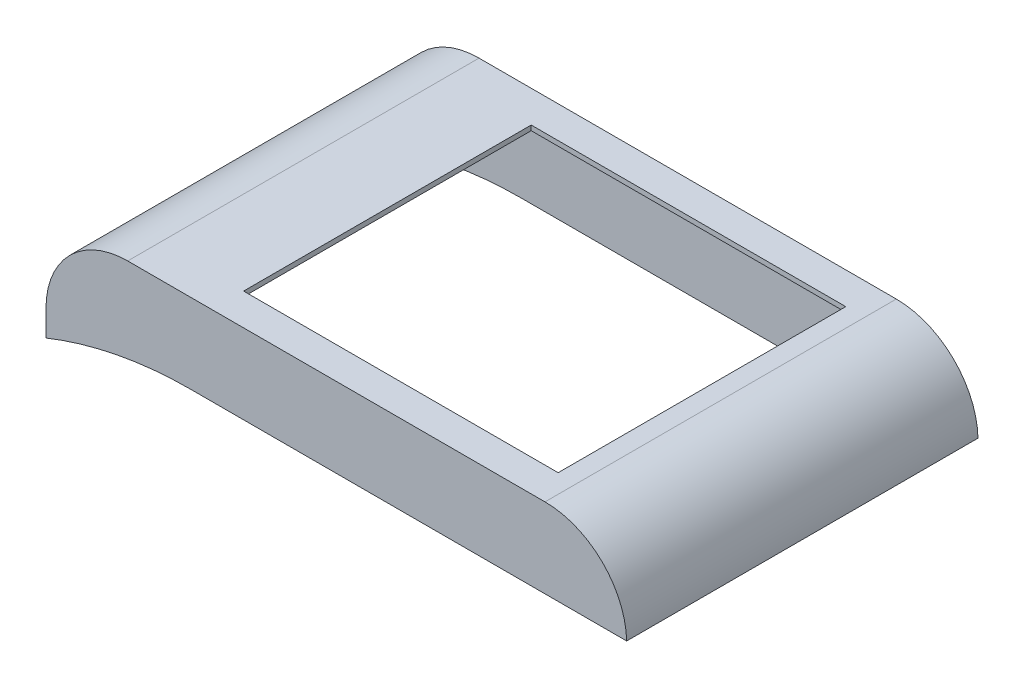
SolidWorks part; units mm, degrees
ref_plane "Front Plane" through (0, 0, 0) normal (0, 0, 1) x (1, 0, 0)
ref_plane "Top Plane" through (0, 0, 0) normal (0, 1, 0) x (1, 0, 0)
ref_plane "Right Plane" through (0, 0, 0) normal (1, 0, 0) x (0, 0, -1)
ref_plane "Plane1" through (0, 0, 21.5) normal (0, 0, 1) x (1, 0, 0)
sketch "Sketch1" plane through (0, 0, 21.5) normal (0, 0, 1) x (1, 0, 0)
  line L0 (21.0747, 0) -> (21.0747, 9.75)
  line L1 (21.0747, 9.75) -> (-49.9953, 9.75)
  line L2 (-49.9953, 9.75) -> (-49.9953, -3.4183)
  line L3 (-32.2824, 0) -> (21.0747, 0)
  arc A0 (-49.9953, -3.4183) -> (-32.2824, 0) centre (-32.2824, -47.6014) cw
  dimension "D2" = 47.6014
  dimension "D1" = 71.07
  dimension "D3" = 53.3571
  dimension "D4" = 9.75
extrude "Boss-Extrude1" add sketch "Sketch1" against normal blind 43
ref_plane "Plane2" through (0, 0, 0) normal (0, -1, 0) x (1, 0, 0)
ref_plane "Plane3" through (0, 8.55, 0) normal (0, 1, 0) x (1, 0, 0)
sketch "Sketch3" plane through (0, 8.55, 0) normal (0, 1, 0) x (1, 0, 0)
  line L0 (18.5747, 19) -> (-47.4953, 19)
  line L1 (-47.4953, 19) -> (-47.4953, -19)
  line L2 (-47.4953, -19) -> (18.5747, -19)
  line L3 (18.5747, -19) -> (18.5747, 19)
extrude "Cut-Extrude1" cut sketch "Sketch3" against normal up to surface (8.55 mm away) up to plane "Plane2"
sketch "Sketch4" plane through (0, 8.55, 0) normal (0, -1, 0) x (1, 0, 0)
  line L0 (-38.2103, -18.5) -> (9.2897, -18.5)
  line L1 (9.2897, -18.5) -> (9.2897, 18.5)
  line L2 (9.2897, 18.5) -> (-38.2103, 18.5)
  line L3 (-38.2103, 18.5) -> (-38.2103, -18.5)
  line L5 (27.7138, 0) -> (14.7168, 0) construction
  line L6 (-14.4603, 21.5) -> (-14.4603, 30.2903) construction
  line L7 (21.0747, 21.5) -> (-49.9953, 21.5) construction
  dimension "D1" = 47.5
  dimension "D2" = 37
extrude "Cut-Extrude2" cut sketch "Sketch4" against normal blind 0.6
sketch "Sketch5" plane through (0, 9.75, 0) normal (0, 1, 0) x (-1, 0, 0)
  line L0 (-8.7897, -17.6) -> (29.7103, -17.6)
  line L1 (29.7103, -17.6) -> (29.7103, 17.6)
  line L2 (29.7103, 17.6) -> (-8.7897, 17.6)
  line L3 (-8.7897, 17.6) -> (-8.7897, -17.6)
  line L4 (-21.0747, 0) -> (-30.6823, 0) construction
  line L5 (-21.0747, -21.5) -> (-21.0747, 21.5) construction
  line L6 (14.4603, 21.5) -> (14.4603, 29.8625) construction
  line L7 (-21.0747, 21.5) -> (49.9953, 21.5) construction
  dimension "D1" = 38.5
  dimension "D2" = 35.2
extrude "Cut-Extrude3" cut sketch "Sketch5" against normal up to next
fillet "Fillet1" radius 7 2 edges at (-47.4953, 8.55, 0) (18.5747, 8.55, 0) tangent propagation no
fillet "Fillet2" radius 10 2 edges at (21.0747, 9.75, 0) (-49.9953, 9.75, 0) tangent propagation no
sketch "Sketch6" plane through (0, 0, 0) normal (0, 1, 0) x (1, 0, 0)
  line L0 (-47.4953, -19) -> (-32.2824, -19) construction
  line L1 (-32.2824, 19) -> (-32.7824, 19)
  line L2 (-32.2824, 19) -> (-32.2824, -19)
  line L3 (-32.2824, -19) -> (-32.7824, -19)
  line L4 (-32.7824, 19) -> (-32.7824, -19)
  dimension "D1" = 0.5
extrude "Cut-Extrude4" cut sketch "Sketch6" against normal blind 10
sketch "Sketch7" plane through (0, 0, 0) normal (0, 1, 0) x (1, 0, 0)
  line L4 (-47.4953, -19) -> (-32.7824, -19)
  line L5 (-32.7824, -19) -> (-32.7824, 19)
  line L6 (-32.7824, 19) -> (-47.4953, 19)
  line L7 (-47.4953, 19) -> (-47.4953, -19)
  line L8 (-47.4953, -19) -> (-32.7824, -19)
  line L9 (-32.7824, -19) -> (-32.7824, 19)
  line L10 (-32.7824, 19) -> (-47.4953, 19)
  line L11 (-47.4953, 19) -> (-47.4953, -19)
  dimension "D1" = 0
extrude "Boss-Extrude2" add sketch "Sketch7" along normal blind 1.5
sketch "Sketch8" plane through (0, 1.5, 0) normal (0, 1, 0) x (1, 0, 0)
  line L4 (-47.4953, 19) -> (-47.4953, -19)
  line L5 (-47.4953, -19) -> (-32.7824, -19)
  line L6 (-32.7824, -19) -> (-32.7824, 19)
  line L7 (-32.7824, 19) -> (-47.4953, 19)
  line L8 (-47.4953, 19) -> (-47.4953, -19)
  line L9 (-47.4953, -19) -> (-32.7824, -19)
  line L10 (-32.7824, -19) -> (-32.7824, 19)
  line L11 (-32.7824, 19) -> (-47.4953, 19)
  dimension "D1" = 0
extrude "Cut-Extrude5" cut sketch "Sketch8" against normal up to next
sketch "Sketch9" plane through (0, 0, 0) normal (0, -1, 0) x (1, 0, 0)
  line L1 (18.5747, 19) -> (3.5747, 19)
  line L2 (18.5747, 19) -> (18.5747, -19)
  line L3 (18.5747, -19) -> (3.5747, -19)
  line L4 (3.5747, 19) -> (3.5747, -19)
  point P6 (0, 0)
  point P7 (0, 0)
  dimension "D1" = 15
extrude "Boss-Extrude3" add sketch "Sketch9" against normal blind 3
